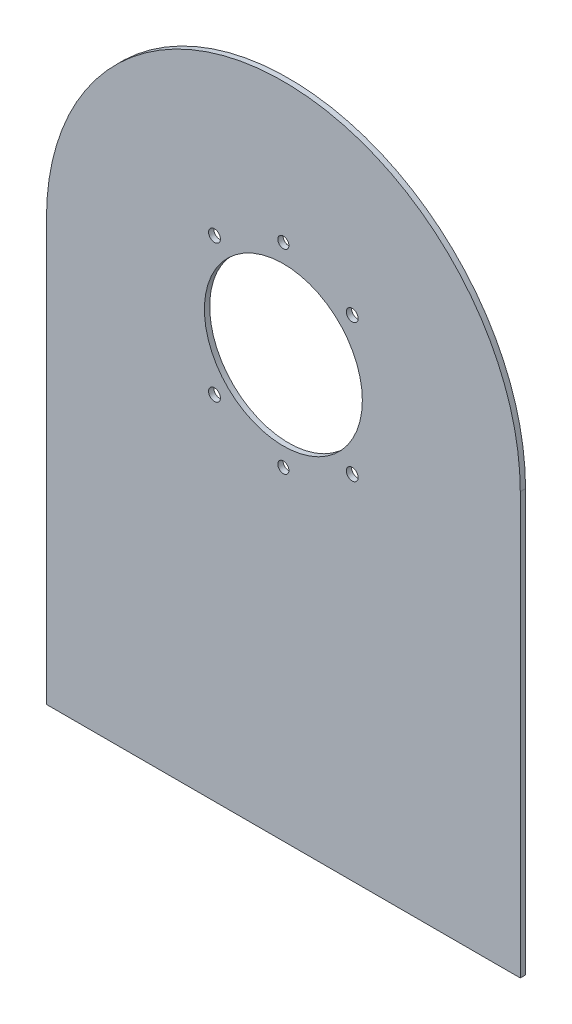
SolidWorks part; units mm, degrees
ref_plane "Face" through (0, 0, 0) normal (0, 0, 1) x (1, 0, 0)
ref_plane "Dessus" through (0, 0, 0) normal (0, 1, 0) x (1, 0, 0)
ref_plane "Droite" through (0, 0, 0) normal (1, 0, 0) x (0, 0, -1)
sketch "Esquisse1" plane through (0, 0, 0) normal (0, 0, 1) x (1, 0, 0)
  line L0 (-90, -160) -> (90, -160)
  line L1 (90, 0) -> (90, -160)
  line L2 (-90, 0) -> (-90, -160)
  arc A0 (90, 0) -> (-90, 0) centre (0, 0) ccw
  circle A1 centre (0, 0) radius 30
  dimension "D1" = 180
  dimension "D3" = 60
  dimension "D2" = 160
extrude "Boss.-Extru.1" add sketch "Esquisse1" along normal blind 2
ref_axis "Axe3" through (0, 0, -80.9) along (0, 0, 1)
sketch "Esquisse2" plane through (0, 0, 2) normal (0, 0, 1) x (1, 0, 0)
  line L0 (0, 0) -> (37, 0) construction
  line L1 (-26.163, 26.163) -> (26.163, -26.163) construction
  line L2 (26.163, 26.163) -> (-26.163, -26.163) construction
  line L3 (0, 37) -> (0, -37) construction
  circle A0 centre (0, 0) radius 37 construction
  circle A1 centre (26.163, 26.163) radius 2.25
  circle A2 centre (-26.163, -26.163) radius 2.25
  circle A3 centre (-26.163, 26.163) radius 2.25
  circle A4 centre (26.163, -26.163) radius 2.25
  circle A5 centre (0, 37) radius 2.1
  circle A6 centre (0, -37) radius 2.1
  dimension "D1" = 74
  dimension "D2" = 45
  dimension "D3" = 45
extrude "Enlèv. mat.-Extru.1" cut sketch "Esquisse2" against normal up to next
sketch "Esquisse4" plane through (0, 0, 0) normal (0, 0, -1) x (-1, 0, 0)
  line L0 (90, -160) -> (-90, -160) construction
  circle A0 centre (-20, -100) radius 2
  circle A1 centre (0, 0) radius 30 construction
  circle A2 centre (20, -100) radius 2
  dimension "D1" = 60
  dimension "D2" = 20
  dimension "D3" = 60
  dimension "D4" = 40
extrude "Goujon M4x20" add sketch "Esquisse4" along normal blind 20
